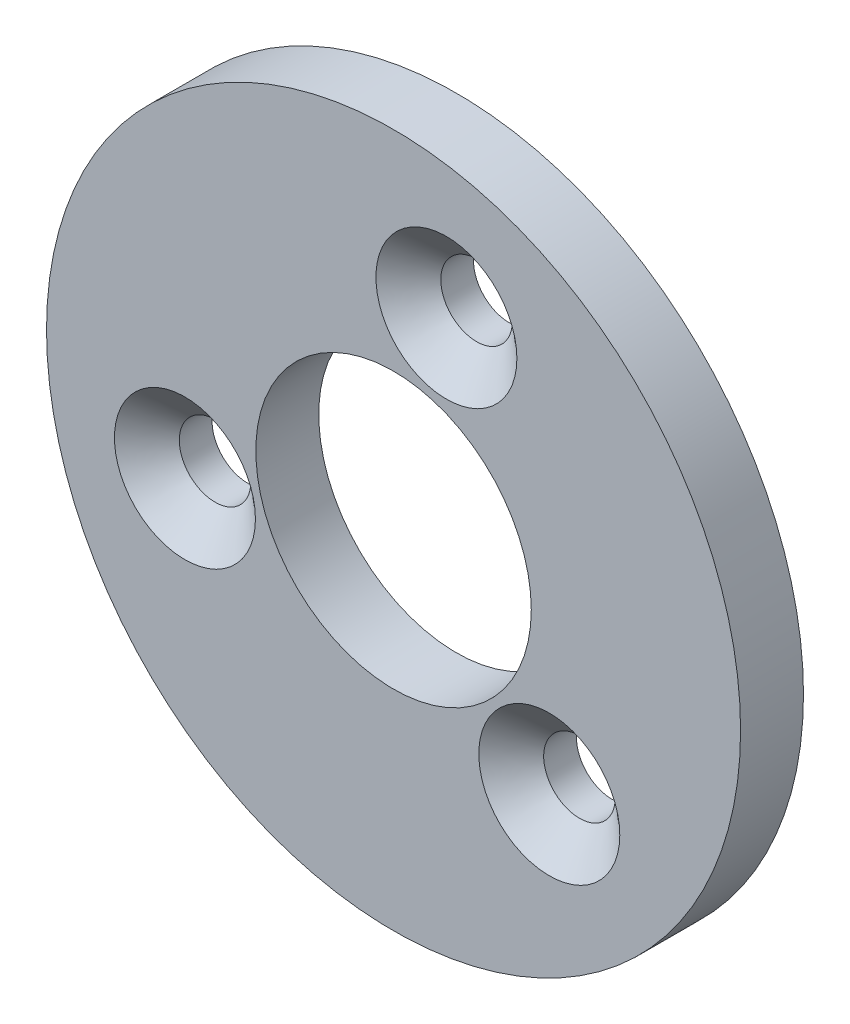
SolidWorks part; units mm, degrees
ref_plane "Front Plane" through (0, 0, 0) normal (0, 0, 1) x (1, 0, 0)
ref_plane "Top Plane" through (0, 0, 0) normal (0, 1, 0) x (1, 0, 0)
ref_plane "Right Plane" through (0, 0, 0) normal (1, 0, 0) x (0, 0, -1)
sketch "Sketch1" plane through (0, 0, 0) normal (0, 0, 1) x (1, 0, 0)
  circle A0 centre (0, 0) radius 16
  dimension "D1" = 32
extrude "Boss-Extrude1" add sketch "Sketch1" along normal blind 2.9
sketch "Sketch2" plane through (0, 0, 2.9) normal (0, 0, 1) x (1, 0, 0)
  circle A3 centre (-9.6176, -2.7388) radius 1.65
  circle A4 centre (-9.6176, -2.7388) radius 1.65
  circle A5 centre (7.1807, -6.9597) radius 1.65
  circle A6 centre (7.1807, -6.9597) radius 1.65
  circle A7 centre (2.437, 9.6985) radius 1.65
  circle A8 centre (2.437, 9.6985) radius 1.65
  dimension "D2" = 0
  dimension "D3" = 0
  dimension "D4" = 0
extrude "Cut-Extrude1" cut sketch "Sketch2" against normal through all
chamfer "Chamfer1" distance 1.6 angle 41 3 edges at (-7.9676, -2.7388, 2.9) (4.087, 9.6985, 2.9) (8.8307, -6.9597, 2.9) first distance on face at (8.8307, -6.9597, 2.9)
sketch "Sketch3" plane through (0, 0, 2.9) normal (0, 0, 1) x (1, 0, 0)
  circle A1 centre (0, 0) radius 6.35
  circle A2 centre (0, 0) radius 6.35
  dimension "D1" = 0
extrude "Cut-Extrude2" cut sketch "Sketch3" against normal through all
equation "\"smallPulleyTeeth\"= 15"
equation "\"largePulleyTeeth\"= 40"
equation "\"eighthThick\"= 2.9mm"
equation "\"sixteenthThick\"= 1.7mm"
equation "\"quarterThick\"=5.9mm"
equation "\"OD\"= 145mm"
equation "\"puckAngle\"= 60.5deg"
equation "\"puckDiam\"= 76.5mm"
equation "\"axlePress\"= 5.9mm"
equation "\"press\"= 0.2mm"
equation "\"wheelClear\"= 0.3mm"
equation "\"10-32clear\"= 4.5mm"
equation "\"D1@Boss-Extrude1\"=\"eighthThick\""
equation "\"D1@Chamfer1\"=(6.5-\"6-32clear\")/2"
equation "\"6-32clear\"= 3.3mm"
equation "\"8-32clear\"= 4.0mm"
